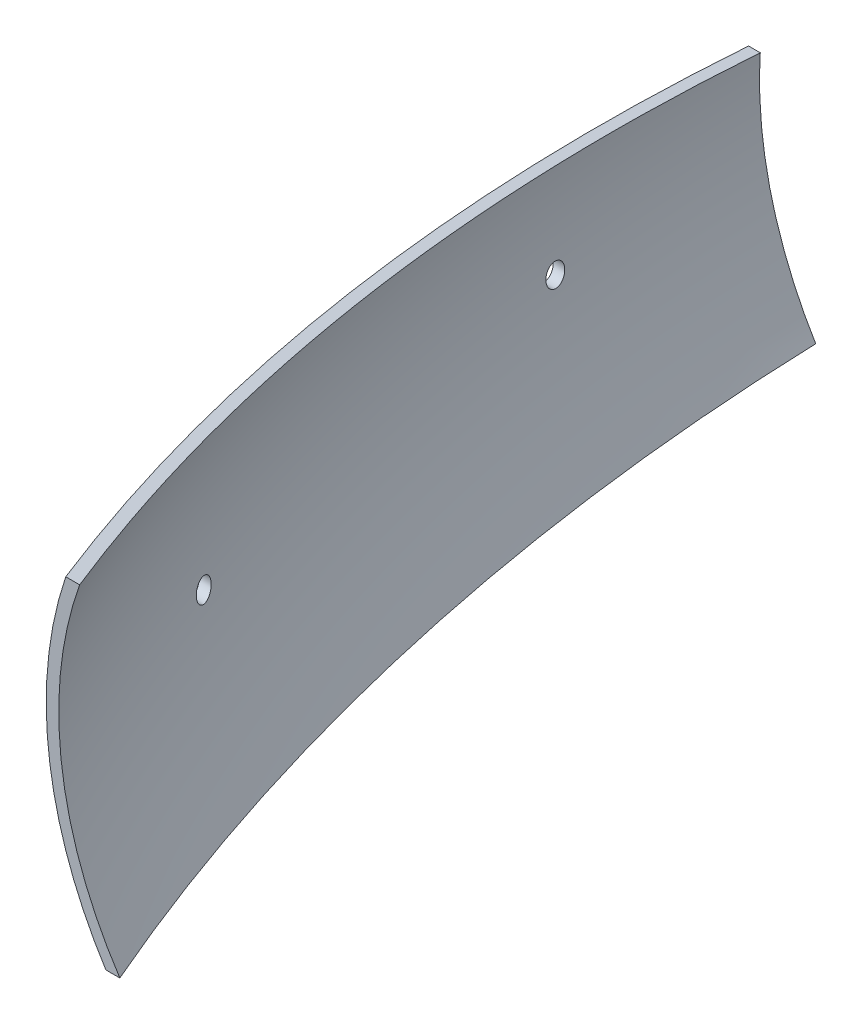
SolidWorks part; units mm, degrees
material "ABS"
ref_plane "Front Plane" through (0, 0, 0) normal (0, 0, 1) x (1, 0, 0)
ref_plane "Top Plane" through (0, 0, 0) normal (0, 1, 0) x (1, 0, 0)
ref_plane "Right Plane" through (0, 0, 0) normal (1, 0, 0) x (0, 0, -1)
sketch "Sketch2" plane through (0, 0, 0) normal (0, 0, 1) x (1, 0, 0)
  line L0 (72.3704, 0) -> (82.3704, 0)
  line L1 (43.5787, 250) -> (53.5787, 250)
  arc A0 (72.3704, 0) -> (43.5787, 250) centre (340.9441, 157.5887) cw
  arc A1 (82.3704, 0) -> (53.5787, 250) centre (338.8585, 156.1968) cw
  dimension "D1" = 250
  dimension "D2" = 10
sketch "Shovel Curvature Axis" plane through (0, 0, 0) normal (0, 0, 1) x (1, 0, 0)
  line L0 (2000, -13.3717) -> (2000, 182.6602)
  line L1 (0, -403.9611) -> (0, 403.9611) construction
  dimension "D1" = 2000
revolve "Revolve1" add sketch "Sketch2" angle 88 about L0
sketch "Sketch5" plane through (0, 0, 0) normal (1, 0, 0) x (0, 0, -1)
  line L0 (-762.4592, 250) -> (-762.4592, 0)
  line L1 (-762.4592, 0) -> (-62.4592, 0)
  line L2 (-62.4592, 0) -> (-62.4592, 175)
  line L3 (-62.4592, 175) -> (-762.4592, 250)
  line L4 (0, 250) -> (-1945.2356, 250) construction
  line L5 (1046.9389, 0) -> (-1046.9389, 0) construction
  line L7 (-2824.2265, 1130.828) -> (2976.3022, 1130.828)
  line L8 (-2824.2265, 1130.828) -> (-2824.2265, -1305.0611)
  line L9 (-2824.2265, -1305.0611) -> (2976.3022, -1305.0611)
  line L10 (2976.3022, 1130.828) -> (2976.3022, -1305.0611)
  line L11 (-2824.2265, 1130.828) -> (2976.3022, -1305.0611) construction
  line L12 (-2824.2265, -1305.0611) -> (2976.3022, 1130.828) construction
  point P8 (76.0379, -87.1165)
  dimension "D1" = 700
  dimension "D2" = 175
extrude "Cut-Extrude2" cut sketch "Sketch5" against normal through all both and the other way through all
sketch "Sketch6" plane through (0, 0, 0) normal (1, 0, 0) x (0, 0, -1)
  line L0 (-587.4592, 120) -> (-237.4592, 120) construction
  line L1 (211.2744, 0) -> (-211.2744, 0) construction
  line L2 (-762.4592, 27.256) -> (-62.4592, 27.256) construction
  line L3 (-762.4592, 250) -> (-762.4592, 0) construction
  line L4 (-62.4592, 0) -> (-62.4592, 175) construction
  line L5 (-412.4592, 27.256) -> (-412.4592, 120) construction
  circle A0 centre (-587.4592, 120) radius 8.3125
  circle A1 centre (-237.4592, 120) radius 8.3125
  dimension "D3" = 16.625
  dimension "D1" = 120
  dimension "D2" = 350
extrude "Cut-Extrude4" cut sketch "Sketch6" along normal through all both
ref_plane "Locating Plane" through (30, 0, 0) normal (1, 0, 0) x (0, 0, -1)
equation "\"shovelWidth\"= 700"
equation "\"D1@Sketch5\"=\"shovelWidth\""
equation "\"holeDiameter\"= 5in / 8 + 0.75"
equation "\"D3@Sketch6\"=\"holeDiameter\""
